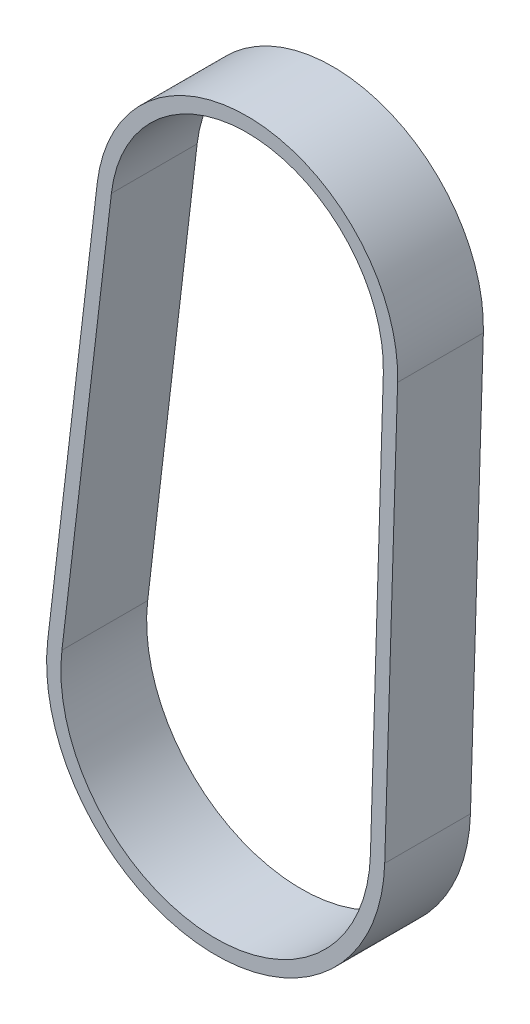
SolidWorks part; units mm, degrees
ref_plane "Front Plane" through (0, 0, 0) normal (0, 0, 1) x (1, 0, 0)
ref_plane "Top Plane" through (0, 0, 0) normal (0, 1, 0) x (1, 0, 0)
ref_plane "Right Plane" through (0, 0, 0) normal (1, 0, 0) x (0, 0, -1)
sketch "Sketch2" plane through (0, 0, 0) normal (0, 0, 1) x (1, 0, 0)
  line L0 (0, 0) -> (1, 0) construction
  line L1 (0, 0) -> (0, 1) construction
  line L4 (-19.4172, -42.4393) -> (-14.2258, 1.6741)
  line L5 (14.3173, -0.4364) -> (12.9639, -44.8336)
  arc A2 (12.9639, -44.8336) -> (-19.4172, -42.4393) centre (-3.2786, -44.3385) cw
  arc A3 (-14.2258, 1.6741) -> (14.3173, -0.4364) centre (0, 0) cw
extrude "Extrude-Thin1" add sketch "Sketch2" along normal blind 9 thin thin type one direction wall 1.5
